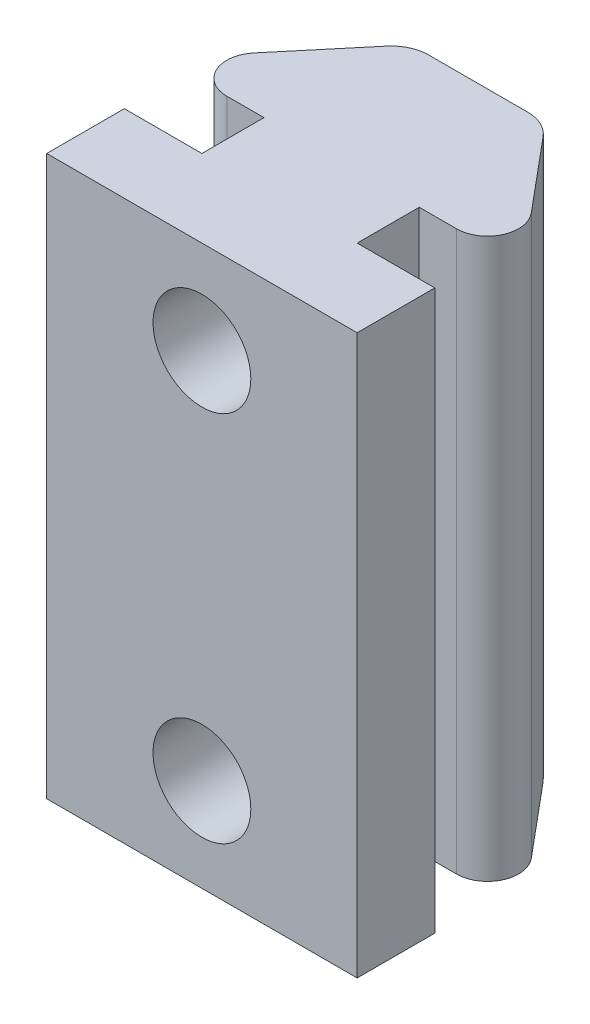
SolidWorks part; units mm, degrees
ref_plane "Front Plane" through (0, 0, 0) normal (0, 0, 1) x (1, 0, 0)
ref_plane "Top Plane" through (0, 0, 0) normal (0, 1, 0) x (1, 0, 0)
ref_plane "Right Plane" through (0, 0, 0) normal (1, 0, 0) x (0, 0, -1)
sketch "Sketch1" plane through (0, 0, 0) normal (0, 0, 1) x (1, 0, 0)
  line L0 (-6.35, 0) -> (6.35, 0) construction
  line L1 (-6.35, -11.43) -> (6.35, -11.43)
  line L2 (-6.35, -11.43) -> (-6.35, 11.43)
  line L3 (-6.35, 11.43) -> (6.35, 11.43)
  line L4 (6.35, -11.43) -> (6.35, 11.43)
  line L5 (-6.35, -11.43) -> (6.35, 11.43) construction
  line L6 (-6.35, 11.43) -> (6.35, -11.43) construction
  line L8 (-6.35, 11.43) -> (0, 11.43)
  point P0 (0, 0)
  dimension "D1" = 22.86
  dimension "D2" = 12.7
extrude "Boss-Extrude1" add sketch "Sketch1" along normal blind 3.175 contours L2 L1 L4 L3
sketch "Sketch2" plane through (0, 11.43, 0) normal (0, 1, 0) x (1, 0, 0)
  line L0 (0, 0) -> (0, 8.128) construction
  line L1 (3.175, 0) -> (3.175, 2.54)
  line L2 (-6.35, 0) -> (6.35, 0) construction
  line L3 (3.175, 2.54) -> (4.6994, 2.54)
  line L4 (5.6737, 4.6247) -> (3.2011, 7.5816)
  line L5 (2.032, 8.128) -> (-2.032, 8.128)
  line L6 (3.175, 0) -> (-3.175, 0)
  line L7 (-3.175, 0) -> (-3.175, 2.54)
  line L8 (-3.175, 2.54) -> (-4.6994, 2.54)
  line L9 (-5.6737, 4.6247) -> (-3.2011, 7.5816)
  arc A0 (3.2011, 7.5816) -> (2.032, 8.128) centre (2.032, 6.604) ccw
  arc A1 (4.6994, 2.54) -> (5.6737, 4.6247) centre (4.6994, 3.81) ccw
  arc A2 (-4.6994, 2.54) -> (-5.6737, 4.6247) centre (-4.6994, 3.81) cw
  arc A3 (-3.2011, 7.5816) -> (-2.032, 8.128) centre (-2.032, 6.604) cw
  point P19 (2.7442, 8.128)
  point P22 (7.4168, 2.54)
  point P25 (-7.4168, 2.54)
  point P28 (-2.7442, 8.128)
  dimension "D5" = 1.524
  dimension "D7" = 1.27
  dimension "D1" = 8.128
  dimension "D2" = 6.35
  dimension "D3" = 5.588
  dimension "D4" = 14.8336
  dimension "D6" = 4.064
extrude "Boss-Extrude2" add sketch "Sketch2" against normal up to surface (22.86 mm away) up to face at (0, -11.43, 1.5875)
sketch "Sketch4" plane through (0, 0, 3.175) normal (0, 0, 1) x (1, 0, 0)
  line L0 (-6.35, 0) -> (6.35, 0) construction
  line L1 (-6.35, -11.43) -> (-6.35, 11.43) construction
  line L2 (6.35, -11.43) -> (6.35, 11.43) construction
  line L3 (-6.35, 11.43) -> (6.35, 11.43) construction
  circle A0 centre (0, 7.62) radius 2
  circle A1 centre (0, -7.62) radius 2
  dimension "D1" = 4
  dimension "D2" = 3.81
extrude "Cut-Extrude1" cut sketch "Sketch4" against normal through all
